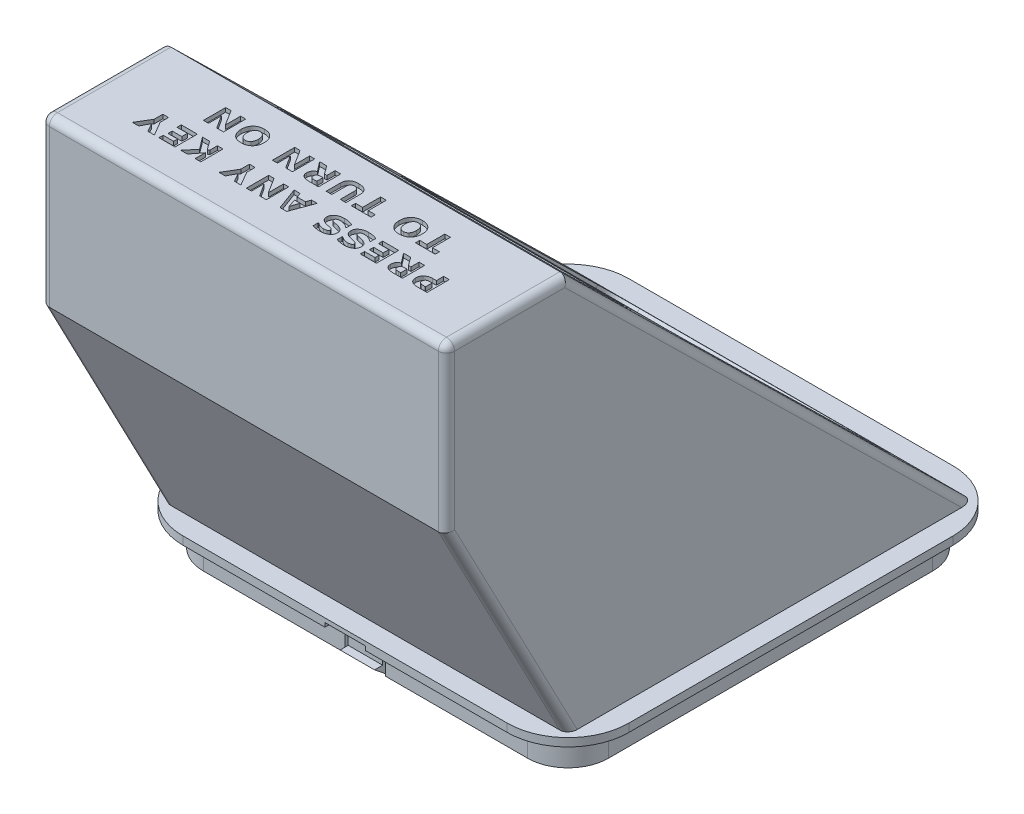
SolidWorks part; units mm, degrees
note: The reader was unsure of these and kept them because the rebuilt part matched: shared geometry of "Sketch5<3>", "Sketch5<4>".
material "ABS"
ref_plane "Front Plane" through (0, 0, 0) normal (0, 0, 1) x (1, 0, 0)
ref_plane "Top Plane" through (0, 0, 0) normal (0, 1, 0) x (1, 0, 0)
ref_plane "Right Plane" through (0, 0, 0) normal (1, 0, 0) x (0, 0, -1)
sketch "Sketch1" plane through (0, 0, 0) normal (0, 1, 0) x (1, 0, 0)
  line L5 (40, -40) -> (-40, -40)
  line L6 (50, -50) -> (-50, -50)
  line L10 (50, -50) -> (50, 50)
  line L11 (50, 50) -> (-50, 50)
  line L12 (-50, -50) -> (-50, 50)
  line L13 (50, -50) -> (-50, 50) construction
  line L14 (50, 50) -> (-50, -50) construction
  line L15 (-40, -40) -> (-40, 40)
  line L16 (40, 40) -> (-40, 40)
  line L17 (40, -40) -> (40, 40)
  point P0 (0, 0)
  dimension "D2" = 100
  dimension "D1" = 100
  dimension "D3" = 10
extrude "Boss-Extrude1" add sketch "Sketch1" along normal blind 6.8
ref_plane "Plane1" through (0, 0, 0) normal (1, 0, 0) x (0, 0, -1)
sketch "Sketch2" plane through (0, 0, 0) normal (1, 0, 0) x (0, 0, -1)
  line L0 (50, 6.8) -> (-50, 104.7796)
  line L2 (42.8557, 6.8) -> (-45, 92.8806)
  line L3 (-45, 8.0281) -> (-45, 6.8)
  line L4 (50, 6.8) -> (42.8557, 6.8)
  line L5 (46.5007, 3.2286) -> (-45, 92.8806) construction
  line L6 (-50, 6.8) -> (-45, 6.8)
  line L7 (-50, 104.7796) -> (-80, 104.7796)
  line L8 (-80, 104.7796) -> (-80, 64.184)
  line L9 (-80, 64.184) -> (-50, 6.8)
  line L10 (-52.0412, 99.7796) -> (-75, 99.7796)
  line L11 (-75, 99.7796) -> (-75, 65.4122)
  line L12 (-75, 65.4122) -> (-50, 17.5921)
  line L13 (-75, 65.4122) -> (-45.569, 9.1165) construction
  line L14 (-50, 17.5921) -> (-45, 8.0281)
  line L15 (-45, 92.8806) -> (-45, 6.8) construction
  line L16 (-50, 17.5921) -> (-50, 6.8)
  line L17 (-50, 104.7796) -> (-50, 6.8) construction
  line L18 (-45, 92.8806) -> (-52.0412, 99.7796)
  line L19 (-50, 99.7796) -> (-75, 99.7796) construction
  dimension "D1" = 140
  dimension "D4" = 30
  dimension "D5" = 117.6
  dimension "D2" = 5
  dimension "D3" = 5
extrude "Boss-Extrude2" add sketch "Sketch2" along normal mid plane 90 contours L14 L16 L6 L3 | L18 L2 L4 L0 L7 L8 L9 L16 L12 L11 L10
sketch "Sketch3" plane through (0, 6.8, 0) normal (0, 1, 0) x (1, 0, 0)
  line L6 (-55, 40) -> (-55, -40)
  line L9 (-235, -50) -> (45, -50)
  line L11 (45, 50) -> (-45, 50)
  line L22 (55, -40) -> (55, 40)
  line L23 (40, 55) -> (-40, 55)
  line L24 (-40, -55) -> (40, -55)
  line L32 (45, -50) -> (50, -50)
  line L33 (50, -50) -> (50, 50)
  line L34 (50, 50) -> (45, 50)
  line L37 (45, 42.8557) -> (-45, 42.8557)
  line L38 (-45, 50) -> (-50, 50)
  line L39 (-50, 50) -> (-50, -50)
  line L40 (-45, 50) -> (-50, 50)
  line L42 (-50, -50) -> (-45, -50)
  line L44 (45, -50) -> (50, -50)
  line L45 (50, -50) -> (50, 50)
  line L46 (50, 50) -> (45, 50)
  line L51 (-50, 50) -> (-50, -50)
  line L55 (-50, -50) -> (-45, -50)
  line L56 (-45, -45) -> (45, -45)
  line L57 (45, -45) -> (45, -50)
  line L58 (45, -45) -> (45, -50)
  line L59 (45, 50) -> (45, 42.8557)
  line L60 (45, 50) -> (45, 42.8557)
  line L61 (-45, 42.8557) -> (-45, 50)
  line L62 (-45, 42.8557) -> (-45, 50)
  line L63 (-45, -50) -> (-45, -45)
  line L64 (-45, -50) -> (-45, -45)
  arc A12 (-40, 55) -> (-55, 40) centre (-40, 40) ccw
  arc A13 (-55, -40) -> (-40, -55) centre (-40, -40) ccw
  arc A14 (40, -55) -> (55, -40) centre (40, -40) ccw
  arc A15 (55, 40) -> (40, 55) centre (40, 40) ccw
  dimension "D1" = 0
extrude "Boss-Extrude3" add sketch "Sketch3" against normal blind 2
sketch "Sketch5" plane through (0, 28.4642, -27.8891) normal (0, 0.7143, -0.6999) x (1, 0, 0)
  line L0 (0, -3.74) -> (0, 3.74) construction
  line L1 (29.5, -50.0447) -> (-29.5, -50.0447)
  line L2 (34.5, -45.0447) -> (34.5, 20.9553)
  line L3 (29.5, 25.9553) -> (-29.5, 25.9553)
  line L4 (-34.5, -45.0447) -> (-34.5, 20.9553)
  line L5 (34.5, -50.0447) -> (-34.5, 25.9553) construction
  line L6 (34.5, 25.9553) -> (-34.5, -50.0447) construction
  line L7 (45, -109.0447) -> (-45, -109.0447) construction
  line L8 (45, 30.9553) -> (-45, 30.9553) construction
  line L9 (-11, 17.6553) -> (11, 17.6553)
  line L10 (-11, 17.6553) -> (-11, 21.1553)
  line L11 (-11, 21.1553) -> (11, 21.1553)
  line L12 (11, 17.6553) -> (11, 21.1553)
  line L13 (-11, 17.6553) -> (11, 21.1553) construction
  line L14 (-11, 21.1553) -> (11, 17.6553) construction
  line L15 (-40, -97.5447) -> (40, -97.5447) construction
  line L16 (-40, -97.5447) -> (-40, -61.5447) construction
  line L17 (-40, -61.5447) -> (40, -61.5447) construction
  line L18 (40, -97.5447) -> (40, -61.5447) construction
  line L19 (-40, -97.5447) -> (40, -61.5447) construction
  line L20 (-40, -61.5447) -> (40, -97.5447) construction
  line L21 (35.5, -45.0447) -> (35.5, 20.9553)
  line L22 (0, -50.0447) -> (0, -109.0447) construction
  line L23 (29.5, 26.9553) -> (-29.5, 26.9553)
  line L24 (-35.5, -45.0447) -> (-35.5, 20.9553)
  line L25 (35.6, -66.7447) -> (-35.6, -66.7447)
  line L26 (35.6, -66.7447) -> (35.6, -90.8447)
  line L27 (35.6, -90.8447) -> (-35.6, -90.8447)
  line L28 (-35.6, -66.7447) -> (-35.6, -90.8447)
  line L29 (35.6, -66.7447) -> (-35.6, -90.8447) construction
  line L30 (35.6, -90.8447) -> (-35.6, -66.7447) construction
  line L31 (29.5, -51.0447) -> (-29.5, -51.0447)
  circle A1 centre (-38.2, -63.7447) radius 1.45
  circle A2 centre (38.2, -63.7447) radius 1.45
  circle A3 centre (-38.2, -63.7447) radius 3.45
  circle A4 centre (38.2, -63.7447) radius 3.45
  arc A5 (-29.5, -50.0447) -> (-34.5, -45.0447) centre (-29.5, -45.0447) cw
  arc A6 (-29.5, 25.9553) -> (-34.5, 20.9553) centre (-29.5, 20.9553) ccw
  arc A7 (34.5, 20.9553) -> (29.5, 25.9553) centre (29.5, 20.9553) ccw
  arc A8 (29.5, -50.0447) -> (34.5, -45.0447) centre (29.5, -45.0447) ccw
  arc A9 (29.5, -51.0447) -> (35.5, -45.0447) centre (29.5, -45.0447) ccw
  arc A10 (35.5, 20.9553) -> (29.5, 26.9553) centre (29.5, 20.9553) ccw
  arc A11 (-29.5, 26.9553) -> (-35.5, 20.9553) centre (-29.5, 20.9553) ccw
  arc A12 (-29.5, -51.0447) -> (-35.5, -45.0447) centre (-29.5, -45.0447) cw
  point P0 (0, -12.0447)
  point P10 (0, 19.4053)
  point P15 (0, -79.5447)
  point P21 (0, 25.9553)
  point P22 (0, -78.7947)
  point P23 (0, -79.5447)
  dimension "D12" = 2.9
  dimension "D17" = 5
  dimension "D1" = 76
  dimension "D2" = 69
  dimension "D3" = 4.8
  dimension "D4" = 22
  dimension "D5" = 3.5
  dimension "D6" = 5
  dimension "D7" = 36
  dimension "D8" = 80
  dimension "D9" = 6.7
  dimension "D10" = 24.1
  dimension "D11" = 71.2
  dimension "D13" = 2.6
  dimension "D14" = 2.6
  dimension "D15" = 3
  dimension "D16" = 2
  dimension "D18" = 1
extrude "Cut-Extrude1" cut sketch "Sketch5" against normal up to surface (5 mm away) contours L25 L28 L27 L26 | L9 L12 L11 L10 up to face at (0, 53.2898, 4.5928)
extrude "Boss-Extrude4" add sketch "Sketch5<3>" against normal offset from surface (7.7 mm away) 7.7 contours A3 A1 | A4 A2 up to face at (0, 83.609, 28.3929)
sketch "Sketch5<3>" plane through (0, 28.4642, -27.8891) normal (0, 0.7143, -0.6999) x (1, 0, 0) same geometry as "Sketch5"
sketch "Sketch7" plane through (0, 24.8928, -24.3898) normal (0, -0.7143, 0.6999) x (1, 0, 0)
  circle A1 centre (-38.2, 63.7447) radius 1.45
  circle A2 centre (-38.2, 63.7447) radius 1.45
  circle A3 centre (38.2, 63.7447) radius 1.45
  circle A4 centre (38.2, 63.7447) radius 1.45
  dimension "D1" = 0
  dimension "D2" = 0
extrude "Cut-Extrude2" cut sketch "Sketch7" against normal blind 2
fillet "Fillet1" radius 10 4 edges at (-50, 2.4, -50) (50, 2.4, -50) (50, 2.4, 50) (-50, 2.4, 50)
sketch "Sketch8" plane through (-45, 0, 0) normal (-1, 0, 0) x (0, 0, 1)
  line L0 (-42.8557, 6.8) -> (45, 6.8)
  line L11 (75, 65.4122) -> (45, 8.0281)
  line L12 (45, 8.0281) -> (45, 6.8)
  line L13 (45, 6.8) -> (50, 6.8)
  line L14 (50, 6.8) -> (80, 64.184)
  line L15 (80, 64.184) -> (80, 104.7796)
  line L16 (80, 104.7796) -> (50, 104.7796)
  line L17 (50, 104.7796) -> (-50, 6.8)
  line L18 (-50, 6.8) -> (-42.8557, 6.8)
  line L19 (-42.8557, 6.8) -> (52.0412, 99.7796)
  line L20 (52.0412, 99.7796) -> (75, 99.7796)
  line L21 (75, 99.7796) -> (75, 65.4122)
  line L24 (45, 6.8) -> (50, 6.8)
  line L25 (50, 6.8) -> (80, 64.184)
  line L26 (80, 64.184) -> (80, 104.7796)
  line L27 (80, 104.7796) -> (50, 104.7796)
  line L28 (50, 104.7796) -> (-50, 6.8)
  line L29 (-50, 6.8) -> (-42.8557, 6.8)
  dimension "D1" = 0
extrude "Boss-Extrude5" add sketch "Sketch8" along normal blind 5
mirror "Mirror1" about plane through (0, 0, 0) normal (1, 0, 0) of "Boss-Extrude5"
fillet "Fillet2" radius 2 9 edges at (0, 104.7796, 80) (50, 104.7796, 65) (50, 84.4818, 80) (-50, 84.4818, 80) (-50, 104.7796, 65) (-50, 35.492, 65) (50, 35.492, 65) (50, 55.7898, 0) (-50, 55.7898, 0)
sketch "Sketch9" plane through (0, 0, 0) normal (0, -1, 0) x (1, 0, 0)
  line L1 (40, -40) -> (-40, -40)
  line L2 (40, -40) -> (40, 40)
  line L3 (40, 40) -> (-40, 40)
  line L4 (-50, 40) -> (-50, -40)
  line L5 (-40, -50) -> (40, -50)
  line L6 (50, -40) -> (50, 40)
  line L7 (40, 50) -> (-40, 50)
  line L8 (-50, 40) -> (-50, -40)
  line L9 (-40, -50) -> (40, -50)
  line L10 (50, -40) -> (50, 40)
  line L11 (40, 50) -> (-40, 50)
  line L12 (-40, -40) -> (-40, 40)
  line L13 (0, 40) -> (0, -40) construction
  line L14 (40, 0) -> (-40, 0) construction
  arc A4 (-50, -40) -> (-40, -50) centre (-40, -40) ccw
  arc A5 (40, -50) -> (50, -40) centre (40, -40) ccw
  arc A6 (50, 40) -> (40, 50) centre (40, 40) ccw
  arc A7 (-40, 50) -> (-50, 40) centre (-40, 40) ccw
  arc A8 (-50, -40) -> (-40, -50) centre (-40, -40) ccw
  arc A9 (40, -50) -> (50, -40) centre (40, -40) ccw
  arc A10 (50, 40) -> (40, 50) centre (40, 40) ccw
  arc A11 (-40, 50) -> (-50, 40) centre (-40, 40) ccw
  point P221 (0, 0)
  dimension "D1" = 0
extrude "Boss-Extrude6" add sketch "Sketch9" along normal offset from surface (3.2 mm away) 8 up to face at (0, 4.8, 0) offset beyond the face yes
extrude "Cut-Extrude3" cut sketch "Sketch5<4>" against normal blind 1 contours L1 A8 L2 A7 L3 A6 L4 A5 L12 L9 L10 L11 | A12 L31 A9 L21 A10 L23 A11 L24 A8 L1 A5 L4 A6 L3 A7 L2
sketch "Sketch5<4>" plane through (0, 28.4642, -27.8891) normal (0, 0.7143, -0.6999) x (1, 0, 0) same geometry as "Sketch5"
sketch "Sketch10" plane through (0, 104.7796, 0) normal (0, 1, 0) x (1, 0, 0)
  line L0 (48, -65.3397) -> (-48, -65.3397) construction
  text T0 "PRESS ANY KEY\r\nTO TURN ON" font "Verdana" height 5.5
extrude "Cut-Extrude4" cut sketch "Sketch10" against normal blind 1
sketch "Sketch11" plane through (0, 0, -50) normal (0, 0, -1) x (-1, 0, 0)
  line L0 (40, -3.2) -> (40, 4.8) construction
  line L1 (-40, -3.2) -> (40, -3.2)
  line L2 (-40, -3.2) -> (-40, -1.2)
  line L3 (-40, -1.2) -> (40, -1.2)
  line L4 (40, -3.2) -> (40, -1.2)
  line L5 (0, -1.2) -> (0, -3.2) construction
  line L6 (-40, -2.2) -> (40, -2.2) construction
  point P168 (0, -2.2)
  dimension "D1" = 2
extrude "Boss-Extrude7" add sketch "Sketch11" along normal blind 3
chamfer "Chamfer1" distance 1 angle 45 1 edges at (0, -1.2, -53)
sketch "Sketch12" plane through (0, -3.2, 0) normal (0, -1, 0) x (1, 0, 0)
  line L0 (-40, 50) -> (40, 50) construction
  line L1 (-5, 50) -> (5, 50)
  line L2 (-5, 50) -> (-5, 45)
  line L3 (-5, 45) -> (5, 45)
  line L4 (5, 50) -> (5, 45)
  line L5 (0, 45) -> (0, 50) construction
  line L6 (-5, 47.5) -> (5, 47.5) construction
  line L7 (0, -3.74) -> (0, 3.74) construction
  point P312 (0, 47.5)
  dimension "D1" = 10
  dimension "D2" = 5
extrude "Cut-Extrude5" cut sketch "Sketch12" against normal up to surface (8 mm away) up to face at (0, 4.8, 0)
sketch "Sketch13" plane through (0, 4.8, 0) normal (0, -1, 0) x (1, 0, 0)
  line L0 (0, -3.74) -> (0, 3.74) construction
  line L1 (-4.25, 50) -> (4.25, 50)
  line L2 (-4.25, 50) -> (-4.25, 48)
  line L3 (-4.25, 48) -> (4.25, 48)
  line L4 (4.25, 50) -> (4.25, 48)
  line L5 (0, 48) -> (0, 50) construction
  line L6 (-4.25, 49) -> (4.25, 49) construction
  line L7 (5, 50) -> (40, 50) construction
  point P108 (0, 49)
  dimension "D1" = 2
  dimension "D2" = 8.5
extrude "Boss-Extrude8" add sketch "Sketch13" along normal up to surface (8 mm away) up to face at (0, -3.2, 0)
sketch "Sketch14" plane through (4.25, 0, 0) normal (1, 0, 0) x (0, 0, -1)
  line L0 (-50, -3.2) -> (-52, -3.2)
  line L1 (-52, -3.2) -> (-52, -1.2)
  line L2 (-52, -1.2) -> (-50, -1.2)
  line L3 (-50, -3.2) -> (-50, 4.8) construction
  line L4 (-50, -3.2) -> (-50, -1.2)
  dimension "D1" = 2
  dimension "D2" = 2
extrude "Boss-Extrude9" add sketch "Sketch14" against normal up to surface (8.5 mm away) up to face at (-4.25, 0.8, 49)
chamfer "Chamfer2" distance 2.5 distance2 2 1 edges at (0, -3.2, 52) first distance on face at (0, -3.2, 50)
sketch "Sketch18" plane through (5, 0, 0) normal (-1, 0, 0) x (0, 0, 1)
  line L0 (50, 4.8) -> (55, 5.8)
  line L1 (55, 5.8) -> (55, 4.8)
  line L2 (55, 4.8) -> (50, 4.8)
  dimension "D1" = 1
extrude "Cut-Extrude6" cut sketch "Sketch18" along normal up to surface (10 mm away) up to face at (-5, 0.8, 47.5)
